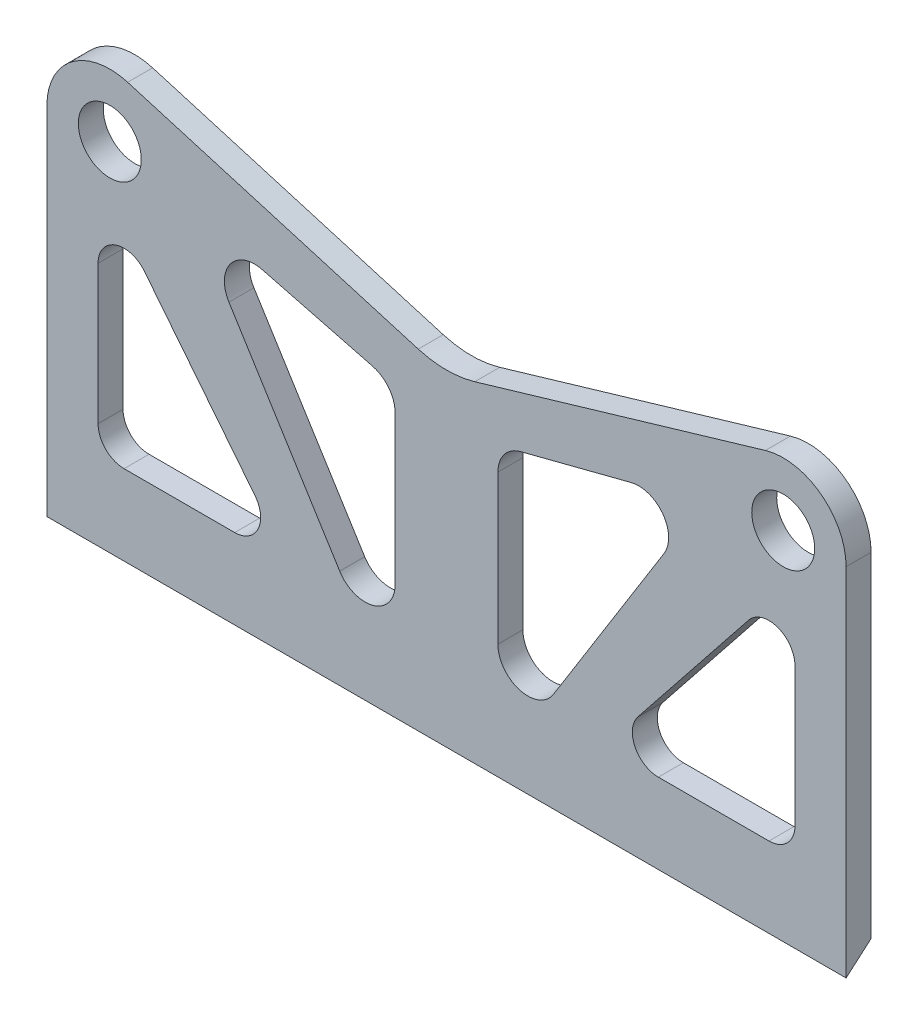
SolidWorks part; units mm, degrees
other "Static 1"
material "AISI 4340 Steel, annealed"
ref_plane "Front Plane" through (0, 0, 0) normal (0, 0, 1) x (1, 0, 0)
ref_plane "Top Plane" through (0, 0, 0) normal (0, 1, 0) x (1, 0, 0)
ref_plane "Right Plane" through (0, 0, 0) normal (1, 0, 0) x (0, 0, -1)
sketch "Sketch1" plane through (0, 0, 1577.6299) normal (0, 0, 1) x (1, 0, 0)
  line L0 (50.7886, 668.0016) -> (50.7886, 617.2016)
  line L1 (175.9802, 617.2016) -> (0, 617.2016) construction
  line L2 (50.7886, 617.2016) -> (-50.7886, 617.2016)
  line L3 (0, 617.2016) -> (0, 663.7057)
  line L4 (0, 663.7057) -> (40.5313, 675.6688)
  line L9 (0, -655.0677) -> (0, 655.0677) construction
  line L10 (-50.7886, 668.0016) -> (-50.7886, 617.2016)
  line L11 (0, 663.7057) -> (-40.5313, 675.6688)
  line L20 (13.5751, 635.3332) -> (27.6548, 657.8993)
  line L21 (23.4718, 663.6056) -> (9.3921, 659.9782)
  line L22 (38.4, 655.9272) -> (24.3401, 638.2654)
  line L23 (26.9235, 632.9069) -> (40.9833, 632.9069)
  line L24 (6.5327, 656.2887) -> (6.5327, 637.35)
  line L25 (44.2853, 636.2089) -> (44.2853, 653.8707)
  line L26 (-44.2853, 636.2089) -> (-44.2853, 653.8707)
  line L27 (-26.9235, 632.9069) -> (-40.9833, 632.9069)
  line L28 (-38.4, 655.9272) -> (-24.3401, 638.2654)
  line L29 (-6.5327, 656.2887) -> (-6.5327, 637.35)
  line L30 (-23.4718, 663.6056) -> (-9.3921, 659.9782)
  line L31 (-13.5751, 635.3332) -> (-27.6548, 657.8993)
  circle A0 centre (42.7944, 668.0016) radius 4
  arc A1 (50.7886, 668.0016) -> (40.5313, 675.6688) centre (42.7944, 668.0016) ccw
  circle A2 centre (-42.7944, 668.0016) radius 4
  arc A3 (-50.7886, 668.0016) -> (-40.5313, 675.6688) centre (-42.7944, 668.0016) cw
  arc A16 (9.3921, 659.9782) -> (6.5327, 656.2887) centre (10.3427, 656.2887) ccw
  arc A17 (6.5327, 637.35) -> (13.5751, 635.3332) centre (10.3427, 637.35) ccw
  arc A18 (27.6548, 657.8993) -> (23.4718, 663.6056) centre (24.4224, 659.9161) ccw
  arc A19 (24.3401, 638.2654) -> (26.9235, 632.9069) centre (26.9235, 636.2089) ccw
  arc A20 (44.2853, 653.8707) -> (38.4, 655.9272) centre (40.9833, 653.8707) ccw
  arc A21 (40.9833, 632.9069) -> (44.2853, 636.2089) centre (40.9833, 636.2089) ccw
  arc A22 (-44.2853, 653.8707) -> (-38.4, 655.9272) centre (-40.9833, 653.8707) cw
  arc A23 (-40.9833, 632.9069) -> (-44.2853, 636.2089) centre (-40.9833, 636.2089) cw
  arc A24 (-24.3401, 638.2654) -> (-26.9235, 632.9069) centre (-26.9235, 636.2089) cw
  arc A25 (-9.3921, 659.9782) -> (-6.5327, 656.2887) centre (-10.3427, 656.2887) cw
  arc A26 (-27.6548, 657.8993) -> (-23.4718, 663.6056) centre (-24.4224, 659.9161) cw
  arc A27 (-6.5327, 637.35) -> (-13.5751, 635.3332) centre (-10.3427, 637.35) cw
  dimension "D1" = 10.3427
  dimension "D3" = 20.1484
  dimension "D4" = 10.3427
  dimension "D7" = 7.62
  dimension "D8" = 7.62
  dimension "D9" = 7.62
  dimension "D10" = 6.604
  dimension "D11" = 6.604
  dimension "D12" = 6.604
  dimension "D2" = 39.0871
  dimension "D5" = 24.4224
  dimension "D6" = 42.7145
  dimension "D13" = 9.8053
  dimension "D14" = 36.6691
  dimension "D15" = 19.0073
  dimension "D16" = 9.8053
  dimension "D17" = 19.0073
  dimension "D18" = 23.8651
extrude "Boss-Extrude1" add sketch "Sketch1" along normal blind 3.175 contours L4 A1 L0 L2 L10 A3 L11
extrude "Cut-Extrude1" cut sketch "Sketch1<8>" along normal blind 20.701 contours A0
sketch "Sketch1<8>" plane through (0, 0, 1577.6299) normal (0, 0, 1) x (1, 0, 0) same geometry as "Sketch1"
extrude "Cut-Extrude2" cut sketch "Sketch1<9>" along normal blind 19.431 contours A2
sketch "Sketch1<9>" plane through (0, 0, 1577.6299) normal (0, 0, 1) x (1, 0, 0) same geometry as "Sketch1"
extrude "Cut-Extrude8" cut sketch "Sketch1<17>" along normal blind 20.193 contours L20 A18 L21 A16 L24 A17 | L28 A24 L27 A23 L26 A22 | L22 A19 L23 A21 L25 A20 | L31 A26 L30 A25 L29 A27
sketch "Sketch1<17>" plane through (0, 0, 1577.6299) normal (0, 0, 1) x (1, 0, 0) same geometry as "Sketch1"
fillet "Fillet1" radius 12.7 1 edges at (0, 663.7057, 1579.2174)
sketch "Sketch5" plane through (50.7886, 0, 0) normal (1, 0, 0) x (0, 0, -1)
  line L0 (-1577.636, 625.4737) -> (-1580.8049, 622.7301)
  line L1 (-1580.8049, 668.0016) -> (-1580.8049, 617.2016) construction
  line L2 (-1580.8049, 622.7301) -> (-1584.5109, 619.5215)
  line L3 (-1584.5109, 619.5215) -> (-1584.5109, 612.3041)
  line L4 (-1584.5109, 612.3041) -> (-1576.0303, 612.3041)
  line L5 (-1576.0303, 612.3041) -> (-1576.0303, 626.8639)
  line L6 (-1577.636, 625.4737) -> (-1576.0303, 626.8639)
extrude "Cut-Extrude9" cut sketch "Sketch5" against normal blind 126.238
